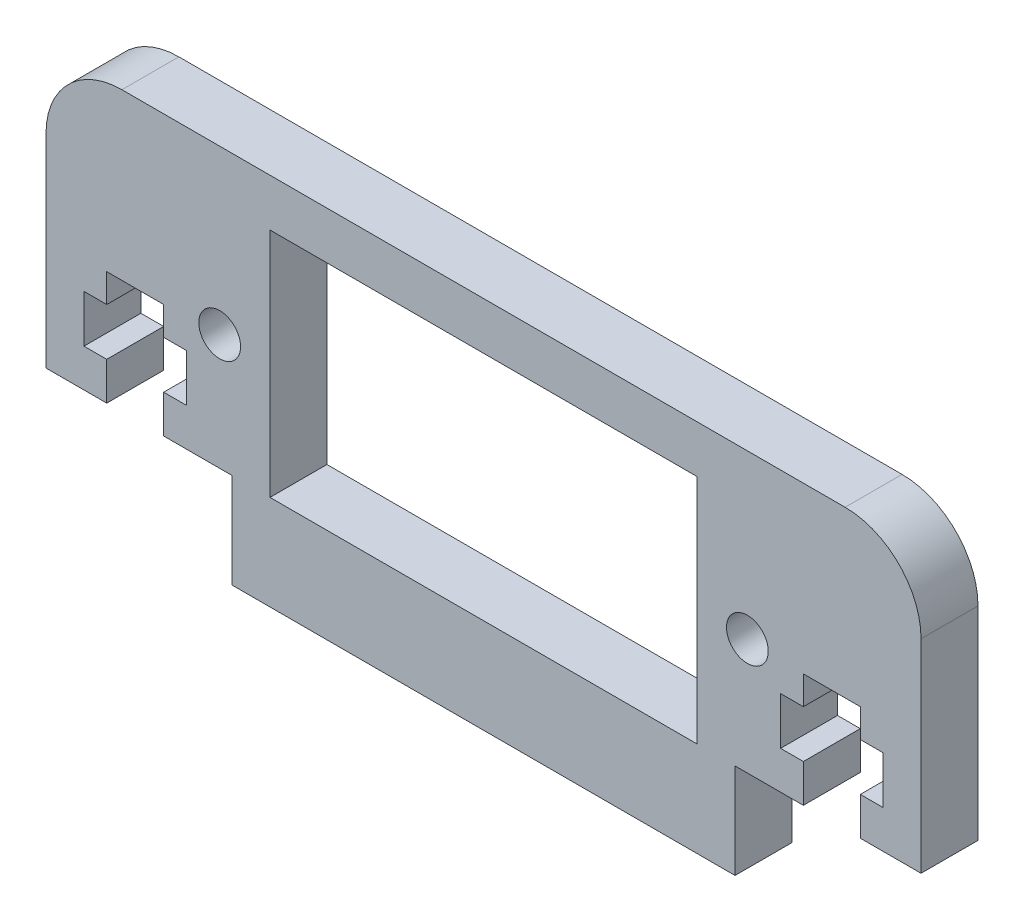
SolidWorks part; units mm, degrees
ref_plane "Front Plane" through (0, 0, 0) normal (0, 0, 1) x (1, 0, 0)
ref_plane "Top Plane" through (0, 0, 0) normal (0, 1, 0) x (1, 0, 0)
ref_plane "Right Plane" through (0, 0, 0) normal (1, 0, 0) x (0, 0, -1)
sketch "Sketch1" plane through (0, 0, 0) normal (0, 0, 1) x (1, 0, 0)
  line L0 (-28.05, -6.1) -> (-23.05, -6.1) construction
  line L1 (-28.05, -6.1) -> (-23.05, -6.1) construction
  line L2 (-11.25, 1.562) -> (-11.25, 5.25) construction
  line L3 (-23.05, -6.1) -> (23.05, -6.1)
  line L4 (-23.05, -6.1) -> (-23.05, 8.6)
  line L5 (-23.05, 8.6) -> (23.05, 8.6)
  line L6 (23.05, -6.1) -> (23.05, 8.6)
  line L7 (-16.05, 0.55) -> (16.05, 0.55) construction
  line L8 (0, 0.55) -> (0, 8.6) construction
  line L9 (-10.4, 6.1) -> (-15.2, 6.1) construction
  line L10 (-16.05, 5.25) -> (-16.05, 6.1) construction
  line L11 (-16.05, 6.1) -> (-15.2, 6.1) construction
  line L12 (-11.25, 6.1) -> (11.25, 6.1)
  line L13 (-11.25, 6.1) -> (-11.25, -6.1)
  line L14 (-11.25, -6.1) -> (11.25, -6.1)
  line L15 (11.25, 6.1) -> (11.25, -6.1)
  line L16 (11.25, 5.25) -> (11.25, -5.25) construction
  arc A0 (-14.8526, -0.55) -> (-14.8526, 0.55) centre (-13.9, 0) ccw construction
  arc A1 (14.8526, 0.55) -> (14.8526, -0.55) centre (13.9, 0) ccw construction
  circle A2 centre (-13.9, 0) radius 1.1
  circle A3 centre (13.9, 0) radius 1.1
  dimension "D1" = 2.5
extrude "Boss-Extrude1" add sketch "Sketch1" along normal blind 3 contours L12 L15 L3 L6 L5 L4 L13 A3 A2 region at (-22.5661, 1.25, 0)
fillet "Fillet1" radius 4 2 edges at (-23.05, 8.6, 1.5) (23.05, 8.6, 1.5)
sketch "Sketch2" plane through (0, 0, 0) normal (0, 0, -1) x (-1, 0, 0)
  line L0 (-18.35, -6.1) -> (-18.35, 14.2115) construction
  line L1 (-11.25, -6.1) -> (-23.05, -6.1) construction
  line L2 (-23.05, -6.1) -> (-23.05, 4.6) construction
  line L3 (-19.85, -0.1) -> (-16.85, -0.1)
  line L4 (-19.85, -0.1) -> (-19.85, -6.1)
  line L5 (-19.85, -6.1) -> (-16.85, -6.1)
  line L6 (-16.85, -0.1) -> (-16.85, -6.1)
  line L7 (-19.85, -0.1) -> (-16.85, -6.1) construction
  line L8 (-19.85, -6.1) -> (-16.85, -0.1) construction
  line L9 (-15.65, -4.1) -> (-21.05, -4.1)
  line L10 (-15.65, -4.1) -> (-15.65, -1.6)
  line L11 (-15.65, -1.6) -> (-21.05, -1.6)
  line L12 (-21.05, -4.1) -> (-21.05, -1.6)
  line L13 (-15.65, -4.1) -> (-21.05, -1.6) construction
  line L14 (-15.65, -1.6) -> (-21.05, -4.1) construction
  line L15 (0, 8.6) -> (0, -13.4545) construction
  line L16 (19.05, 8.6) -> (-19.05, 8.6) construction
  line L17 (15.65, -1.6) -> (21.05, -4.1) construction
  line L18 (15.65, -4.1) -> (21.05, -1.6) construction
  line L19 (19.85, -6.1) -> (16.85, -0.1) construction
  line L20 (19.85, -0.1) -> (16.85, -6.1) construction
  line L21 (21.05, -4.1) -> (21.05, -1.6)
  line L22 (15.65, -1.6) -> (21.05, -1.6)
  line L23 (15.65, -4.1) -> (15.65, -1.6)
  line L24 (15.65, -4.1) -> (21.05, -4.1)
  line L25 (16.85, -0.1) -> (16.85, -6.1)
  line L26 (19.85, -6.1) -> (16.85, -6.1)
  line L27 (19.85, -0.1) -> (19.85, -6.1)
  line L28 (19.85, -0.1) -> (16.85, -0.1)
  point P4 (-18.35, -3.1)
  point P9 (-18.35, -2.85)
  point P29 (18.35, -2.85)
  point P30 (18.35, -3.1)
  line M8 (-23.05, -6.1) -> (-11.25, -6.1)
  line M12 (11.25, -6.1) -> (23.05, -6.1)
  dimension "D1" = 3
  dimension "D2" = 2.5
  dimension "D3" = 2
  dimension "D4" = 5.4
  dimension "D5" = 2
  dimension "D6" = 6
extrude "Cut-Extrude1" cut sketch "Sketch2" against normal through all and the other way blind 10 contours L12 L9 L4 L11 | L11 L6 L3 L4 | L10 L11 L6 L9 | L6 L11 L4 L9 | L6 L9 L4 M8 | L27 L28 L25 L22 | L25 L22 L23 L24 | L27 L22 L25 L24 | L27 L24 L25 M12 | L22 L27 L24 L21 region at (18.35, -0.85, 0) region at (18.35, -2.85, 0) region at (20.45, -2.85, 0) region at (16.25, -2.85, 0) region at (18.35, -5.1, 0) region at (-20.45, -2.85, 0) region at (-18.35, -5.1, 0) region at (-18.35, -2.85, 0) region at (-18.35, -0.85, 0) region at (-16.25, -2.85, 0)
sketch "Sketch3" plane through (0, 0, 0) normal (0, 0, -1) x (-1, 0, 0)
  line L0 (-11.25, -6.1) -> (-16.85, -6.1) construction
  line L1 (-13.25, -6.1) -> (13.25, -6.1)
  line L2 (-13.25, -6.1) -> (-13.25, -11.1)
  line L3 (-13.25, -11.1) -> (13.25, -11.1)
  line L4 (13.25, -6.1) -> (13.25, -11.1)
  line L5 (28.05, -11.1) -> (10.55, -11.1) construction
  line L6 (-11.25, 6.1) -> (-11.25, -6.1) construction
  line L7 (11.25, 6.1) -> (11.25, -6.1) construction
  dimension "D1" = 2
  dimension "D2" = 2
extrude "Boss-Extrude2" add sketch "Sketch3" against normal blind 3
